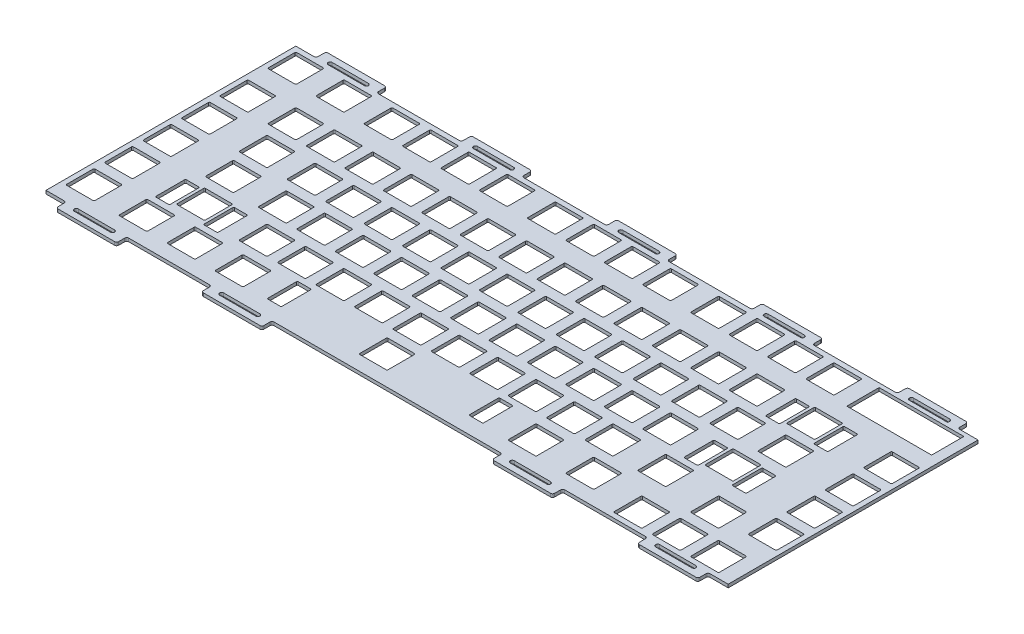
SolidWorks part; units mm, degrees
ref_plane "Front" through (0, 0, 0) normal (0, 0, 1) x (1, 0, 0)
ref_plane "Top" through (0, 0, 0) normal (0, 1, 0) x (1, 0, 0)
ref_plane "Right" through (0, 0, 0) normal (1, 0, 0) x (0, 0, -1)
sketch "Sketch4" plane through (0, 0, 0) normal (0, 1, 0) x (1, 0, 0)
  line L5 (291.1375, -2) -> (333.1375, -2)
  line L6 (291.1375, -2) -> (291.1375, -18)
  line L7 (291.1375, -18) -> (333.1375, -18)
  line L12 (333.1375, -2) -> (333.1375, -18)
  line L202 (0, 0) -> (338.1375, 0)
  line L781 (311.3, -102.25) -> (298.3, -102.25)
  line L782 (335.1125, -97.4875) -> (322.1125, -97.4875)
  line L783 (316.85, -120.8) -> (316.85, -107.8)
  line L784 (330.35, -121.3) -> (317.35, -121.3)
  line L785 (330.85, -107.8) -> (330.85, -120.8)
  line L786 (317.35, -107.3) -> (330.35, -107.3)
  line L787 (297.8, -120.8) -> (297.8, -107.8)
  line L788 (311.3, -121.3) -> (298.3, -121.3)
  line L789 (311.8, -107.8) -> (311.8, -120.8)
  line L790 (298.3, -107.3) -> (311.3, -107.3)
  line L791 (263.675, -116.5375) -> (250.675, -116.5375)
  line L792 (278.75, -120.8) -> (278.75, -107.8)
  line L793 (292.25, -121.3) -> (279.25, -121.3)
  line L794 (292.75, -107.8) -> (292.75, -120.8)
  line L795 (279.25, -107.3) -> (292.25, -107.3)
  line L796 (235.1, -116.5375) -> (222.1, -116.5375)
  line L797 (83.9875, -26.3375) -> (96.9875, -26.3375)
  line L798 (97.4875, -26.8375) -> (97.4875, -39.8375)
  line L799 (96.9875, -40.3375) -> (83.9875, -40.3375)
  line L800 (83.4875, -39.8375) -> (83.4875, -26.8375)
  line L801 (102.5375, -39.8375) -> (102.5375, -26.8375)
  line L802 (116.0375, -40.3375) -> (103.0375, -40.3375)
  line L803 (116.5375, -26.8375) -> (116.5375, -39.8375)
  line L804 (103.0375, -26.3375) -> (116.0375, -26.3375)
  line L805 (188.2625, -58.8875) -> (188.2625, -45.8875)
  line L806 (201.7625, -59.3875) -> (188.7625, -59.3875)
  line L807 (202.2625, -45.8875) -> (202.2625, -58.8875)
  line L808 (188.7625, -45.3875) -> (201.7625, -45.3875)
  line L809 (207.3125, -58.8875) -> (207.3125, -45.8875)
  line L810 (220.8125, -59.3875) -> (207.8125, -59.3875)
  line L811 (221.3125, -45.8875) -> (221.3125, -58.8875)
  line L812 (207.8125, -45.3875) -> (220.8125, -45.3875)
  line L813 (321.6125, -77.9375) -> (321.6125, -64.9375)
  line L814 (335.1125, -78.4375) -> (322.1125, -78.4375)
  line L815 (335.6125, -64.9375) -> (335.6125, -77.9375)
  line L816 (322.1125, -64.4375) -> (335.1125, -64.4375)
  line L817 (148.2812, -102.5375) -> (161.2812, -102.5375)
  line L818 (161.7812, -103.0375) -> (161.7812, -116.0375)
  line L819 (161.2812, -116.5375) -> (148.2812, -116.5375)
  line L820 (147.7812, -116.0375) -> (147.7812, -103.0375)
  line L821 (208.2812, -101.0375) -> (208.2812, -115.0375)
  line L822 (201.7812, -100.5375) -> (207.7812, -100.5375)
  line L823 (201.2812, -115.0375) -> (201.2812, -101.0375)
  line L824 (207.7812, -115.5375) -> (201.7812, -115.5375)
  line L825 (64.4375, -39.8375) -> (64.4375, -26.8375)
  line L826 (77.9375, -40.3375) -> (64.9375, -40.3375)
  line L827 (78.4375, -26.8375) -> (78.4375, -39.8375)
  line L828 (64.9375, -26.3375) -> (77.9375, -26.3375)
  line L829 (169.2125, -58.8875) -> (169.2125, -45.8875)
  line L830 (182.7125, -59.3875) -> (169.7125, -59.3875)
  line L831 (183.2125, -45.8875) -> (183.2125, -58.8875)
  line L832 (169.7125, -45.3875) -> (182.7125, -45.3875)
  line L833 (273.1932, -65.4375) -> (279.1932, -65.4375)
  line L834 (279.6932, -65.9375) -> (279.6932, -79.9375)
  line L835 (279.1932, -80.4375) -> (273.1932, -80.4375)
  line L836 (272.6932, -79.9375) -> (272.6932, -65.9375)
  line L837 (296.5692, -79.9375) -> (296.5692, -65.9375)
  line L838 (303.0692, -80.4375) -> (297.0692, -80.4375)
  line L839 (303.5692, -65.9375) -> (303.5692, -79.9375)
  line L840 (297.0692, -65.4375) -> (303.0692, -65.4375)
  line L841 (76.3437, -116.0375) -> (76.3437, -103.0375)
  line L842 (89.8437, -116.5375) -> (76.8437, -116.5375)
  line L843 (90.3437, -103.0375) -> (90.3437, -116.0375)
  line L844 (76.8437, -102.5375) -> (89.8437, -102.5375)
  line L845 (45.3875, -39.8375) -> (45.3875, -26.8375)
  line L846 (58.8875, -40.3375) -> (45.8875, -40.3375)
  line L847 (59.3875, -26.8375) -> (59.3875, -39.8375)
  line L848 (45.8875, -26.3375) -> (58.8875, -26.3375)
  line L849 (131.6125, -45.3875) -> (144.6125, -45.3875)
  line L850 (145.1125, -45.8875) -> (145.1125, -58.8875)
  line L851 (144.6125, -59.3875) -> (131.6125, -59.3875)
  line L852 (131.1125, -58.8875) -> (131.1125, -45.8875)
  line L853 (150.1625, -58.8875) -> (150.1625, -45.8875)
  line L854 (163.6625, -59.3875) -> (150.6625, -59.3875)
  line L855 (164.1625, -45.8875) -> (164.1625, -58.8875)
  line L856 (150.6625, -45.3875) -> (163.6625, -45.3875)
  line L857 (281.1312, -77.9375) -> (281.1312, -64.9375)
  line L858 (294.6312, -78.4375) -> (281.6312, -78.4375)
  line L859 (295.1312, -64.9375) -> (295.1312, -77.9375)
  line L860 (281.6312, -64.4375) -> (294.6312, -64.4375)
  line L861 (52.5312, -116.0375) -> (52.5312, -103.0375)
  line L862 (66.0312, -116.5375) -> (53.0312, -116.5375)
  line L863 (66.5312, -103.0375) -> (66.5312, -116.0375)
  line L864 (53.0312, -102.5375) -> (66.0312, -102.5375)
  line L865 (3.025, -26.3375) -> (16.025, -26.3375)
  line L866 (16.525, -26.8375) -> (16.525, -39.8375)
  line L867 (16.025, -40.3375) -> (3.025, -40.3375)
  line L868 (2.525, -39.8375) -> (2.525, -26.8375)
  line L869 (26.3375, -39.8375) -> (26.3375, -26.8375)
  line L870 (39.8375, -40.3375) -> (26.8375, -40.3375)
  line L871 (40.3375, -26.8375) -> (40.3375, -39.8375)
  line L872 (26.8375, -26.3375) -> (39.8375, -26.3375)
  line L873 (112.0625, -58.8875) -> (112.0625, -45.8875)
  line L874 (125.5625, -59.3875) -> (112.5625, -59.3875)
  line L875 (126.0625, -45.8875) -> (126.0625, -58.8875)
  line L876 (112.5625, -45.3875) -> (125.5625, -45.3875)
  line L877 (250.175, -77.9375) -> (250.175, -64.9375)
  line L878 (263.675, -78.4375) -> (250.675, -78.4375)
  line L879 (264.175, -64.9375) -> (264.175, -77.9375)
  line L880 (250.675, -64.4375) -> (263.675, -64.4375)
  line L881 (3.025, -102.5375) -> (16.025, -102.5375)
  line L882 (16.525, -103.0375) -> (16.525, -116.0375)
  line L883 (16.025, -116.5375) -> (3.025, -116.5375)
  line L884 (2.525, -116.0375) -> (2.525, -103.0375)
  line L885 (28.7187, -116.0375) -> (28.7187, -103.0375)
  line L886 (42.2187, -116.5375) -> (29.2187, -116.5375)
  line L887 (42.7187, -103.0375) -> (42.7187, -116.0375)
  line L888 (29.2187, -102.5375) -> (42.2187, -102.5375)
  line L893 (93.0125, -58.8875) -> (93.0125, -45.8875)
  line L894 (106.5125, -59.3875) -> (93.5125, -59.3875)
  line L895 (107.0125, -45.8875) -> (107.0125, -58.8875)
  line L896 (93.5125, -45.3875) -> (106.5125, -45.3875)
  line L897 (212.575, -64.4375) -> (225.575, -64.4375)
  line L898 (226.075, -64.9375) -> (226.075, -77.9375)
  line L899 (225.575, -78.4375) -> (212.575, -78.4375)
  line L900 (212.075, -77.9375) -> (212.075, -64.9375)
  line L901 (231.125, -77.9375) -> (231.125, -64.9375)
  line L902 (244.625, -78.4375) -> (231.625, -78.4375)
  line L903 (245.125, -64.9375) -> (245.125, -77.9375)
  line L904 (231.625, -64.4375) -> (244.625, -64.4375)
  line L905 (297.8, -101.75) -> (297.8, -88.75)
  line L906 (311.8, -88.75) -> (311.8, -101.75)
  line L907 (298.3, -88.25) -> (311.3, -88.25)
  line L912 (55.4125, -45.3875) -> (68.4125, -45.3875)
  line L913 (68.9125, -45.8875) -> (68.9125, -58.8875)
  line L914 (68.4125, -59.3875) -> (55.4125, -59.3875)
  line L915 (54.9125, -58.8875) -> (54.9125, -45.8875)
  line L916 (73.9625, -58.8875) -> (73.9625, -45.8875)
  line L917 (87.4625, -59.3875) -> (74.4625, -59.3875)
  line L918 (87.9625, -45.8875) -> (87.9625, -58.8875)
  line L919 (74.4625, -45.3875) -> (87.4625, -45.3875)
  line L920 (193.025, -77.9375) -> (193.025, -64.9375)
  line L921 (206.525, -78.4375) -> (193.525, -78.4375)
  line L922 (207.025, -64.9375) -> (207.025, -77.9375)
  line L923 (193.525, -64.4375) -> (206.525, -64.4375)
  line L924 (321.6125, -96.9875) -> (321.6125, -83.9875)
  line L925 (335.6125, -83.9875) -> (335.6125, -96.9875)
  line L926 (322.1125, -83.4875) -> (335.1125, -83.4875)
  line L927 (269.725, -2.525) -> (282.725, -2.525)
  line L928 (283.225, -3.025) -> (283.225, -16.025)
  line L929 (282.725, -16.525) -> (269.725, -16.525)
  line L930 (269.225, -16.025) -> (269.225, -3.025)
  line L935 (31.1, -58.8875) -> (31.1, -45.8875)
  line L936 (44.6, -59.3875) -> (31.6, -59.3875)
  line L937 (45.1, -45.8875) -> (45.1, -58.8875)
  line L938 (31.6, -45.3875) -> (44.6, -45.3875)
  line L939 (173.975, -77.9375) -> (173.975, -64.9375)
  line L940 (187.475, -78.4375) -> (174.475, -78.4375)
  line L941 (187.975, -64.9375) -> (187.975, -77.9375)
  line L942 (174.475, -64.4375) -> (187.475, -64.4375)
  line L943 (241.15, -83.4875) -> (254.15, -83.4875)
  line L944 (254.65, -83.9875) -> (254.65, -96.9875)
  line L945 (254.15, -97.4875) -> (241.15, -97.4875)
  line L946 (240.65, -96.9875) -> (240.65, -83.9875)
  line L947 (266.8437, -96.9875) -> (266.8437, -83.9875)
  line L948 (280.3437, -97.4875) -> (267.3437, -97.4875)
  line L949 (280.8437, -83.9875) -> (280.8437, -96.9875)
  line L950 (267.3437, -83.4875) -> (280.3437, -83.4875)
  line L951 (250.175, -16.025) -> (250.175, -3.025)
  line L952 (263.675, -16.525) -> (250.675, -16.525)
  line L953 (264.175, -3.025) -> (264.175, -16.025)
  line L954 (250.675, -2.525) -> (263.675, -2.525)
  line L955 (2.525, -58.8875) -> (2.525, -45.8875)
  line L956 (16.025, -59.3875) -> (3.025, -59.3875)
  line L957 (16.525, -45.8875) -> (16.525, -58.8875)
  line L958 (3.025, -45.3875) -> (16.025, -45.3875)
  line L959 (136.375, -64.4375) -> (149.375, -64.4375)
  line L960 (149.875, -64.9375) -> (149.875, -77.9375)
  line L961 (149.375, -78.4375) -> (136.375, -78.4375)
  line L962 (135.875, -77.9375) -> (135.875, -64.9375)
  line L963 (154.925, -77.9375) -> (154.925, -64.9375)
  line L964 (168.425, -78.4375) -> (155.425, -78.4375)
  line L965 (168.925, -64.9375) -> (168.925, -77.9375)
  line L966 (155.425, -64.4375) -> (168.425, -64.4375)
  line L967 (221.6, -96.9875) -> (221.6, -83.9875)
  line L968 (235.1, -97.4875) -> (222.1, -97.4875)
  line L969 (235.6, -83.9875) -> (235.6, -96.9875)
  line L970 (222.1, -83.4875) -> (235.1, -83.4875)
  line L971 (231.125, -16.025) -> (231.125, -3.025)
  line L972 (244.625, -16.525) -> (231.625, -16.525)
  line L973 (245.125, -3.025) -> (245.125, -16.025)
  line L974 (231.625, -2.525) -> (244.625, -2.525)
  line L975 (299.4505, -27.3375) -> (305.4505, -27.3375)
  line L976 (305.9505, -27.8375) -> (305.9505, -41.8375)
  line L977 (305.4505, -42.3375) -> (299.4505, -42.3375)
  line L978 (298.9505, -41.8375) -> (298.9505, -27.8375)
  line L979 (321.6125, -39.8375) -> (321.6125, -26.8375)
  line L980 (335.1125, -40.3375) -> (322.1125, -40.3375)
  line L981 (335.6125, -26.8375) -> (335.6125, -39.8375)
  line L982 (322.1125, -26.3375) -> (335.1125, -26.3375)
  line L983 (116.825, -77.9375) -> (116.825, -64.9375)
  line L984 (130.325, -78.4375) -> (117.325, -78.4375)
  line L985 (130.825, -64.9375) -> (130.825, -77.9375)
  line L986 (117.325, -64.4375) -> (130.325, -64.4375)
  line L987 (202.55, -96.9875) -> (202.55, -83.9875)
  line L988 (216.05, -97.4875) -> (203.05, -97.4875)
  line L989 (216.55, -83.9875) -> (216.55, -96.9875)
  line L990 (203.05, -83.4875) -> (216.05, -83.4875)
  line L991 (188.7625, -2.525) -> (201.7625, -2.525)
  line L992 (202.2625, -3.025) -> (202.2625, -16.025)
  line L993 (201.7625, -16.525) -> (188.7625, -16.525)
  line L994 (188.2625, -16.025) -> (188.2625, -3.025)
  line L995 (212.075, -16.025) -> (212.075, -3.025)
  line L996 (225.575, -16.525) -> (212.575, -16.525)
  line L997 (226.075, -3.025) -> (226.075, -16.025)
  line L998 (212.575, -2.525) -> (225.575, -2.525)
  line L999 (275.0745, -41.8375) -> (275.0745, -27.8375)
  line L1000 (281.5745, -42.3375) -> (275.5745, -42.3375)
  line L1001 (282.0745, -27.8375) -> (282.0745, -41.8375)
  line L1002 (275.5745, -27.3375) -> (281.5745, -27.3375)
  line L1003 (97.775, -77.9375) -> (97.775, -64.9375)
  line L1004 (111.275, -78.4375) -> (98.275, -78.4375)
  line L1005 (111.775, -64.9375) -> (111.775, -77.9375)
  line L1006 (98.275, -64.4375) -> (111.275, -64.4375)
  line L1007 (164.95, -83.4875) -> (177.95, -83.4875)
  line L1008 (178.45, -83.9875) -> (178.45, -96.9875)
  line L1009 (177.95, -97.4875) -> (164.95, -97.4875)
  line L1010 (164.45, -96.9875) -> (164.45, -83.9875)
  line L1011 (183.5, -96.9875) -> (183.5, -83.9875)
  line L1012 (197, -97.4875) -> (184, -97.4875)
  line L1013 (197.5, -83.9875) -> (197.5, -96.9875)
  line L1014 (184, -83.4875) -> (197, -83.4875)
  line L1015 (169.2125, -16.025) -> (169.2125, -3.025)
  line L1016 (182.7125, -16.525) -> (169.7125, -16.525)
  line L1017 (183.2125, -3.025) -> (183.2125, -16.025)
  line L1018 (169.7125, -2.525) -> (182.7125, -2.525)
  line L1019 (283.5125, -39.8375) -> (283.5125, -26.8375)
  line L1020 (297.0125, -40.3375) -> (284.0125, -40.3375)
  line L1021 (297.5125, -26.8375) -> (297.5125, -39.8375)
  line L1022 (284.0125, -26.3375) -> (297.0125, -26.3375)
  line L1023 (60.175, -64.4375) -> (73.175, -64.4375)
  line L1024 (73.675, -64.9375) -> (73.675, -77.9375)
  line L1025 (73.175, -78.4375) -> (60.175, -78.4375)
  line L1026 (59.675, -77.9375) -> (59.675, -64.9375)
  line L1027 (78.725, -77.9375) -> (78.725, -64.9375)
  line L1028 (92.225, -78.4375) -> (79.225, -78.4375)
  line L1029 (92.725, -64.9375) -> (92.725, -77.9375)
  line L1030 (79.225, -64.4375) -> (92.225, -64.4375)
  line L1031 (145.4, -96.9875) -> (145.4, -83.9875)
  line L1032 (158.9, -97.4875) -> (145.9, -97.4875)
  line L1033 (159.4, -83.9875) -> (159.4, -96.9875)
  line L1034 (145.9, -83.4875) -> (158.9, -83.4875)
  line L1035 (150.1625, -16.025) -> (150.1625, -3.025)
  line L1036 (163.6625, -16.525) -> (150.6625, -16.525)
  line L1037 (164.1625, -3.025) -> (164.1625, -16.025)
  line L1038 (150.6625, -2.525) -> (163.6625, -2.525)
  line L1039 (236.3875, -26.3375) -> (249.3875, -26.3375)
  line L1040 (249.8875, -26.8375) -> (249.8875, -39.8375)
  line L1041 (249.3875, -40.3375) -> (236.3875, -40.3375)
  line L1042 (235.8875, -39.8375) -> (235.8875, -26.8375)
  line L1043 (254.9375, -39.8375) -> (254.9375, -26.8375)
  line L1044 (268.4375, -40.3375) -> (255.4375, -40.3375)
  line L1045 (268.9375, -26.8375) -> (268.9375, -39.8375)
  line L1046 (255.4375, -26.3375) -> (268.4375, -26.3375)
  line L1047 (33.4812, -77.9375) -> (33.4812, -64.9375)
  line L1048 (46.9812, -78.4375) -> (33.9812, -78.4375)
  line L1049 (47.4812, -64.9375) -> (47.4812, -77.9375)
  line L1050 (33.9812, -64.4375) -> (46.9812, -64.4375)
  line L1051 (126.35, -96.9875) -> (126.35, -83.9875)
  line L1052 (139.85, -97.4875) -> (126.85, -97.4875)
  line L1053 (140.35, -83.9875) -> (140.35, -96.9875)
  line L1054 (126.85, -83.4875) -> (139.85, -83.4875)
  line L1055 (107.8, -2.525) -> (120.8, -2.525)
  line L1056 (121.3, -3.025) -> (121.3, -16.025)
  line L1057 (120.8, -16.525) -> (107.8, -16.525)
  line L1058 (107.3, -16.025) -> (107.3, -3.025)
  line L1059 (131.1125, -16.025) -> (131.1125, -3.025)
  line L1060 (144.6125, -16.525) -> (131.6125, -16.525)
  line L1061 (145.1125, -3.025) -> (145.1125, -16.025)
  line L1062 (131.6125, -2.525) -> (144.6125, -2.525)
  line L1063 (216.8375, -39.8375) -> (216.8375, -26.8375)
  line L1064 (230.3375, -40.3375) -> (217.3375, -40.3375)
  line L1065 (230.8375, -26.8375) -> (230.8375, -39.8375)
  line L1066 (217.3375, -26.3375) -> (230.3375, -26.3375)
  line L1067 (2.525, -77.9375) -> (2.525, -64.9375)
  line L1068 (16.025, -78.4375) -> (3.025, -78.4375)
  line L1069 (16.525, -64.9375) -> (16.525, -77.9375)
  line L1070 (3.025, -64.4375) -> (16.025, -64.4375)
  line L1071 (88.75, -83.4875) -> (101.75, -83.4875)
  line L1072 (102.25, -83.9875) -> (102.25, -96.9875)
  line L1073 (101.75, -97.4875) -> (88.75, -97.4875)
  line L1074 (88.25, -96.9875) -> (88.25, -83.9875)
  line L1075 (107.3, -96.9875) -> (107.3, -83.9875)
  line L1076 (120.8, -97.4875) -> (107.8, -97.4875)
  line L1077 (121.3, -83.9875) -> (121.3, -96.9875)
  line L1078 (107.8, -83.4875) -> (120.8, -83.4875)
  line L1079 (0, -123.825) -> (0, 0)
  line L1080 (338.1375, 0) -> (338.1375, -123.825)
  line L1081 (338.1375, -123.825) -> (0, -123.825)
  line L1082 (88.25, -16.025) -> (88.25, -3.025)
  line L1083 (101.75, -16.525) -> (88.75, -16.525)
  line L1084 (102.25, -3.025) -> (102.25, -16.025)
  line L1085 (88.75, -2.525) -> (101.75, -2.525)
  line L1086 (197.7875, -39.8375) -> (197.7875, -26.8375)
  line L1087 (211.2875, -40.3375) -> (198.2875, -40.3375)
  line L1088 (211.7875, -26.8375) -> (211.7875, -39.8375)
  line L1089 (198.2875, -26.3375) -> (211.2875, -26.3375)
  line L1090 (288.775, -45.3875) -> (301.775, -45.3875)
  line L1091 (302.275, -45.8875) -> (302.275, -58.8875)
  line L1092 (301.775, -59.3875) -> (288.775, -59.3875)
  line L1093 (288.275, -58.8875) -> (288.275, -45.8875)
  line L1094 (321.6125, -58.8875) -> (321.6125, -45.8875)
  line L1095 (335.1125, -59.3875) -> (322.1125, -59.3875)
  line L1096 (335.6125, -45.8875) -> (335.6125, -58.8875)
  line L1097 (322.1125, -45.3875) -> (335.1125, -45.3875)
  line L1098 (69.2, -96.9875) -> (69.2, -83.9875)
  line L1099 (82.7, -97.4875) -> (69.7, -97.4875)
  line L1100 (83.2, -83.9875) -> (83.2, -96.9875)
  line L1101 (69.7, -83.4875) -> (82.7, -83.4875)
  line L1102 (69.2, -16.025) -> (69.2, -3.025)
  line L1103 (82.7, -16.525) -> (69.7, -16.525)
  line L1104 (83.2, -3.025) -> (83.2, -16.025)
  line L1105 (69.7, -2.525) -> (82.7, -2.525)
  line L1106 (160.1875, -26.3375) -> (173.1875, -26.3375)
  line L1107 (173.6875, -26.8375) -> (173.6875, -39.8375)
  line L1108 (173.1875, -40.3375) -> (160.1875, -40.3375)
  line L1109 (159.6875, -39.8375) -> (159.6875, -26.8375)
  line L1110 (178.7375, -39.8375) -> (178.7375, -26.8375)
  line L1111 (192.2375, -40.3375) -> (179.2375, -40.3375)
  line L1112 (192.7375, -26.8375) -> (192.7375, -39.8375)
  line L1113 (179.2375, -26.3375) -> (192.2375, -26.3375)
  line L1114 (264.4625, -58.8875) -> (264.4625, -45.8875)
  line L1115 (277.9625, -59.3875) -> (264.9625, -59.3875)
  line L1116 (278.4625, -45.8875) -> (278.4625, -58.8875)
  line L1117 (264.9625, -45.3875) -> (277.9625, -45.3875)
  line L1118 (53.6817, -98.9875) -> (53.6817, -84.9875)
  line L1119 (60.1817, -99.4875) -> (54.1817, -99.4875)
  line L1120 (60.6817, -84.9875) -> (60.6817, -98.9875)
  line L1121 (54.1817, -84.4875) -> (60.1817, -84.4875)
  line L1122 (250.675, -102.5375) -> (263.675, -102.5375)
  line L1123 (264.175, -103.0375) -> (264.175, -116.0375)
  line L1124 (250.175, -116.0375) -> (250.175, -103.0375)
  line L1125 (26.8375, -2.525) -> (39.8375, -2.525)
  line L1126 (40.3375, -3.025) -> (40.3375, -16.025)
  line L1127 (39.8375, -16.525) -> (26.8375, -16.525)
  line L1128 (26.3375, -16.025) -> (26.3375, -3.025)
  line L1129 (50.15, -16.025) -> (50.15, -3.025)
  line L1130 (63.65, -16.525) -> (50.65, -16.525)
  line L1131 (64.15, -3.025) -> (64.15, -16.025)
  line L1132 (50.65, -2.525) -> (63.65, -2.525)
  line L1133 (140.6375, -39.8375) -> (140.6375, -26.8375)
  line L1134 (154.1375, -40.3375) -> (141.1375, -40.3375)
  line L1135 (154.6375, -26.8375) -> (154.6375, -39.8375)
  line L1136 (141.1375, -26.3375) -> (154.1375, -26.3375)
  line L1137 (245.4125, -58.8875) -> (245.4125, -45.8875)
  line L1138 (258.9125, -59.3875) -> (245.9125, -59.3875)
  line L1139 (259.4125, -45.8875) -> (259.4125, -58.8875)
  line L1140 (245.9125, -45.3875) -> (258.9125, -45.3875)
  line L1141 (38.7437, -83.4875) -> (51.7437, -83.4875)
  line L1142 (52.2437, -83.9875) -> (52.2437, -96.9875)
  line L1143 (51.7437, -97.4875) -> (38.7437, -97.4875)
  line L1144 (38.2437, -96.9875) -> (38.2437, -83.9875)
  line L1145 (29.8057, -98.9875) -> (29.8057, -84.9875)
  line L1146 (36.3057, -99.4875) -> (30.3057, -99.4875)
  line L1147 (36.8057, -84.9875) -> (36.8057, -98.9875)
  line L1148 (30.3057, -84.4875) -> (36.3057, -84.4875)
  line L1149 (221.6, -116.0375) -> (221.6, -103.0375)
  line L1150 (235.6, -103.0375) -> (235.6, -116.0375)
  line L1151 (222.1, -102.5375) -> (235.1, -102.5375)
  line L1152 (121.5875, -39.8375) -> (121.5875, -26.8375)
  line L1153 (135.0875, -40.3375) -> (122.0875, -40.3375)
  line L1154 (135.5875, -26.8375) -> (135.5875, -39.8375)
  line L1155 (122.0875, -26.3375) -> (135.0875, -26.3375)
  line L1156 (226.3625, -58.8875) -> (226.3625, -45.8875)
  line L1157 (239.8625, -59.3875) -> (226.8625, -59.3875)
  line L1158 (240.3625, -45.8875) -> (240.3625, -58.8875)
  line L1159 (226.8625, -45.3875) -> (239.8625, -45.3875)
  line L1160 (2.525, -96.9875) -> (2.525, -83.9875)
  line L1161 (16.025, -97.4875) -> (3.025, -97.4875)
  line L1162 (16.525, -83.9875) -> (16.525, -96.9875)
  line L1163 (3.025, -83.4875) -> (16.025, -83.4875)
  line L1164 (108.2812, -101.0375) -> (108.2812, -115.0375)
  line L1165 (101.7812, -100.5375) -> (107.7812, -100.5375)
  line L1166 (101.2812, -115.0375) -> (101.2812, -101.0375)
  line L1167 (107.7812, -115.5375) -> (101.7812, -115.5375)
  line L1168 (16.525, -16.025) -> (16.525, -3.025)
  line L1169 (3.025, -16.525) -> (16.025, -16.525)
  line L1170 (2.525, -3.025) -> (2.525, -16.025)
  line L1171 (16.025, -2.525) -> (3.025, -2.525)
  arc A776 (298.3, -102.25) -> (297.8, -101.75) centre (298.3, -101.75) cw
  arc A777 (311.8, -101.75) -> (311.3, -102.25) centre (311.3, -101.75) cw
  arc A778 (322.1125, -97.4875) -> (321.6125, -96.9875) centre (322.1125, -96.9875) cw
  arc A779 (335.6125, -96.9875) -> (335.1125, -97.4875) centre (335.1125, -96.9875) cw
  arc A780 (316.85, -107.8) -> (317.35, -107.3) centre (317.35, -107.8) cw
  arc A781 (317.35, -121.3) -> (316.85, -120.8) centre (317.35, -120.8) cw
  arc A782 (330.85, -120.8) -> (330.35, -121.3) centre (330.35, -120.8) cw
  arc A783 (330.35, -107.3) -> (330.85, -107.8) centre (330.35, -107.8) cw
  arc A784 (297.8, -107.8) -> (298.3, -107.3) centre (298.3, -107.8) cw
  arc A785 (298.3, -121.3) -> (297.8, -120.8) centre (298.3, -120.8) cw
  arc A786 (311.8, -120.8) -> (311.3, -121.3) centre (311.3, -120.8) cw
  arc A787 (311.3, -107.3) -> (311.8, -107.8) centre (311.3, -107.8) cw
  arc A788 (264.175, -116.0375) -> (263.675, -116.5375) centre (263.675, -116.0375) cw
  arc A789 (250.675, -116.5375) -> (250.175, -116.0375) centre (250.675, -116.0375) cw
  arc A790 (278.75, -107.8) -> (279.25, -107.3) centre (279.25, -107.8) cw
  arc A791 (279.25, -121.3) -> (278.75, -120.8) centre (279.25, -120.8) cw
  arc A792 (292.75, -120.8) -> (292.25, -121.3) centre (292.25, -120.8) cw
  arc A793 (292.25, -107.3) -> (292.75, -107.8) centre (292.25, -107.8) cw
  arc A794 (222.1, -116.5375) -> (221.6, -116.0375) centre (222.1, -116.0375) cw
  arc A795 (235.6, -116.0375) -> (235.1, -116.5375) centre (235.1, -116.0375) cw
  arc A796 (2.525, -3.025) -> (3.025, -2.525) centre (3.025, -3.025) cw
  arc A797 (16.025, -2.525) -> (16.525, -3.025) centre (16.025, -3.025) cw
  arc A798 (3.025, -16.525) -> (2.525, -16.025) centre (3.025, -16.025) cw
  arc A799 (16.525, -16.025) -> (16.025, -16.525) centre (16.025, -16.025) cw
  arc A800 (83.4875, -26.8375) -> (83.9875, -26.3375) centre (83.9875, -26.8375) cw
  arc A801 (96.9875, -26.3375) -> (97.4875, -26.8375) centre (96.9875, -26.8375) cw
  arc A802 (97.4875, -39.8375) -> (96.9875, -40.3375) centre (96.9875, -39.8375) cw
  arc A803 (83.9875, -40.3375) -> (83.4875, -39.8375) centre (83.9875, -39.8375) cw
  arc A804 (102.5375, -26.8375) -> (103.0375, -26.3375) centre (103.0375, -26.8375) cw
  arc A805 (103.0375, -40.3375) -> (102.5375, -39.8375) centre (103.0375, -39.8375) cw
  arc A806 (116.5375, -39.8375) -> (116.0375, -40.3375) centre (116.0375, -39.8375) cw
  arc A807 (116.0375, -26.3375) -> (116.5375, -26.8375) centre (116.0375, -26.8375) cw
  arc A808 (188.2625, -45.8875) -> (188.7625, -45.3875) centre (188.7625, -45.8875) cw
  arc A809 (188.7625, -59.3875) -> (188.2625, -58.8875) centre (188.7625, -58.8875) cw
  arc A810 (202.2625, -58.8875) -> (201.7625, -59.3875) centre (201.7625, -58.8875) cw
  arc A811 (201.7625, -45.3875) -> (202.2625, -45.8875) centre (201.7625, -45.8875) cw
  arc A812 (207.3125, -45.8875) -> (207.8125, -45.3875) centre (207.8125, -45.8875) cw
  arc A813 (207.8125, -59.3875) -> (207.3125, -58.8875) centre (207.8125, -58.8875) cw
  arc A814 (221.3125, -58.8875) -> (220.8125, -59.3875) centre (220.8125, -58.8875) cw
  arc A815 (220.8125, -45.3875) -> (221.3125, -45.8875) centre (220.8125, -45.8875) cw
  arc A816 (321.6125, -64.9375) -> (322.1125, -64.4375) centre (322.1125, -64.9375) cw
  arc A817 (322.1125, -78.4375) -> (321.6125, -77.9375) centre (322.1125, -77.9375) cw
  arc A818 (335.6125, -77.9375) -> (335.1125, -78.4375) centre (335.1125, -77.9375) cw
  arc A819 (335.1125, -64.4375) -> (335.6125, -64.9375) centre (335.1125, -64.9375) cw
  arc A820 (147.7812, -103.0375) -> (148.2812, -102.5375) centre (148.2812, -103.0375) cw
  arc A821 (161.2812, -102.5375) -> (161.7812, -103.0375) centre (161.2812, -103.0375) cw
  arc A822 (161.7812, -116.0375) -> (161.2812, -116.5375) centre (161.2812, -116.0375) cw
  arc A823 (148.2812, -116.5375) -> (147.7812, -116.0375) centre (148.2812, -116.0375) cw
  arc A824 (208.2812, -115.0375) -> (207.7812, -115.5375) centre (207.7812, -115.0375) cw
  arc A825 (207.7812, -100.5375) -> (208.2812, -101.0375) centre (207.7812, -101.0375) cw
  arc A826 (201.2812, -101.0375) -> (201.7812, -100.5375) centre (201.7812, -101.0375) cw
  arc A827 (201.7812, -115.5375) -> (201.2812, -115.0375) centre (201.7812, -115.0375) cw
  arc A828 (64.4375, -26.8375) -> (64.9375, -26.3375) centre (64.9375, -26.8375) cw
  arc A829 (64.9375, -40.3375) -> (64.4375, -39.8375) centre (64.9375, -39.8375) cw
  arc A830 (78.4375, -39.8375) -> (77.9375, -40.3375) centre (77.9375, -39.8375) cw
  arc A831 (77.9375, -26.3375) -> (78.4375, -26.8375) centre (77.9375, -26.8375) cw
  arc A832 (169.2125, -45.8875) -> (169.7125, -45.3875) centre (169.7125, -45.8875) cw
  arc A833 (169.7125, -59.3875) -> (169.2125, -58.8875) centre (169.7125, -58.8875) cw
  arc A834 (183.2125, -58.8875) -> (182.7125, -59.3875) centre (182.7125, -58.8875) cw
  arc A835 (182.7125, -45.3875) -> (183.2125, -45.8875) centre (182.7125, -45.8875) cw
  arc A836 (272.6932, -65.9375) -> (273.1932, -65.4375) centre (273.1932, -65.9375) cw
  arc A837 (279.1932, -65.4375) -> (279.6932, -65.9375) centre (279.1932, -65.9375) cw
  arc A838 (279.6932, -79.9375) -> (279.1932, -80.4375) centre (279.1932, -79.9375) cw
  arc A839 (273.1932, -80.4375) -> (272.6932, -79.9375) centre (273.1932, -79.9375) cw
  arc A840 (296.5692, -65.9375) -> (297.0692, -65.4375) centre (297.0692, -65.9375) cw
  arc A841 (297.0692, -80.4375) -> (296.5692, -79.9375) centre (297.0692, -79.9375) cw
  arc A842 (303.5692, -79.9375) -> (303.0692, -80.4375) centre (303.0692, -79.9375) cw
  arc A843 (303.0692, -65.4375) -> (303.5692, -65.9375) centre (303.0692, -65.9375) cw
  arc A844 (76.3437, -103.0375) -> (76.8437, -102.5375) centre (76.8437, -103.0375) cw
  arc A845 (76.8437, -116.5375) -> (76.3437, -116.0375) centre (76.8437, -116.0375) cw
  arc A846 (90.3437, -116.0375) -> (89.8437, -116.5375) centre (89.8437, -116.0375) cw
  arc A847 (89.8437, -102.5375) -> (90.3437, -103.0375) centre (89.8437, -103.0375) cw
  arc A848 (45.3875, -26.8375) -> (45.8875, -26.3375) centre (45.8875, -26.8375) cw
  arc A849 (45.8875, -40.3375) -> (45.3875, -39.8375) centre (45.8875, -39.8375) cw
  arc A850 (59.3875, -39.8375) -> (58.8875, -40.3375) centre (58.8875, -39.8375) cw
  arc A851 (58.8875, -26.3375) -> (59.3875, -26.8375) centre (58.8875, -26.8375) cw
  arc A852 (131.1125, -45.8875) -> (131.6125, -45.3875) centre (131.6125, -45.8875) cw
  arc A853 (144.6125, -45.3875) -> (145.1125, -45.8875) centre (144.6125, -45.8875) cw
  arc A854 (145.1125, -58.8875) -> (144.6125, -59.3875) centre (144.6125, -58.8875) cw
  arc A855 (131.6125, -59.3875) -> (131.1125, -58.8875) centre (131.6125, -58.8875) cw
  arc A856 (150.1625, -45.8875) -> (150.6625, -45.3875) centre (150.6625, -45.8875) cw
  arc A857 (150.6625, -59.3875) -> (150.1625, -58.8875) centre (150.6625, -58.8875) cw
  arc A858 (164.1625, -58.8875) -> (163.6625, -59.3875) centre (163.6625, -58.8875) cw
  arc A859 (163.6625, -45.3875) -> (164.1625, -45.8875) centre (163.6625, -45.8875) cw
  arc A860 (281.1312, -64.9375) -> (281.6312, -64.4375) centre (281.6312, -64.9375) cw
  arc A861 (281.6312, -78.4375) -> (281.1312, -77.9375) centre (281.6312, -77.9375) cw
  arc A862 (295.1312, -77.9375) -> (294.6312, -78.4375) centre (294.6312, -77.9375) cw
  arc A863 (294.6312, -64.4375) -> (295.1312, -64.9375) centre (294.6312, -64.9375) cw
  arc A864 (52.5312, -103.0375) -> (53.0312, -102.5375) centre (53.0312, -103.0375) cw
  arc A865 (53.0312, -116.5375) -> (52.5312, -116.0375) centre (53.0312, -116.0375) cw
  arc A866 (66.5312, -116.0375) -> (66.0312, -116.5375) centre (66.0312, -116.0375) cw
  arc A867 (66.0312, -102.5375) -> (66.5312, -103.0375) centre (66.0312, -103.0375) cw
  arc A868 (2.525, -26.8375) -> (3.025, -26.3375) centre (3.025, -26.8375) cw
  arc A869 (16.025, -26.3375) -> (16.525, -26.8375) centre (16.025, -26.8375) cw
  arc A870 (16.525, -39.8375) -> (16.025, -40.3375) centre (16.025, -39.8375) cw
  arc A871 (3.025, -40.3375) -> (2.525, -39.8375) centre (3.025, -39.8375) cw
  arc A872 (26.3375, -26.8375) -> (26.8375, -26.3375) centre (26.8375, -26.8375) cw
  arc A873 (26.8375, -40.3375) -> (26.3375, -39.8375) centre (26.8375, -39.8375) cw
  arc A874 (40.3375, -39.8375) -> (39.8375, -40.3375) centre (39.8375, -39.8375) cw
  arc A875 (39.8375, -26.3375) -> (40.3375, -26.8375) centre (39.8375, -26.8375) cw
  arc A876 (112.0625, -45.8875) -> (112.5625, -45.3875) centre (112.5625, -45.8875) cw
  arc A877 (112.5625, -59.3875) -> (112.0625, -58.8875) centre (112.5625, -58.8875) cw
  arc A878 (126.0625, -58.8875) -> (125.5625, -59.3875) centre (125.5625, -58.8875) cw
  arc A879 (125.5625, -45.3875) -> (126.0625, -45.8875) centre (125.5625, -45.8875) cw
  arc A880 (250.175, -64.9375) -> (250.675, -64.4375) centre (250.675, -64.9375) cw
  arc A881 (250.675, -78.4375) -> (250.175, -77.9375) centre (250.675, -77.9375) cw
  arc A882 (264.175, -77.9375) -> (263.675, -78.4375) centre (263.675, -77.9375) cw
  arc A883 (263.675, -64.4375) -> (264.175, -64.9375) centre (263.675, -64.9375) cw
  arc A884 (2.525, -103.0375) -> (3.025, -102.5375) centre (3.025, -103.0375) cw
  arc A885 (16.025, -102.5375) -> (16.525, -103.0375) centre (16.025, -103.0375) cw
  arc A886 (16.525, -116.0375) -> (16.025, -116.5375) centre (16.025, -116.0375) cw
  arc A887 (3.025, -116.5375) -> (2.525, -116.0375) centre (3.025, -116.0375) cw
  arc A888 (28.7187, -103.0375) -> (29.2187, -102.5375) centre (29.2187, -103.0375) cw
  arc A889 (29.2187, -116.5375) -> (28.7187, -116.0375) centre (29.2187, -116.0375) cw
  arc A890 (42.7187, -116.0375) -> (42.2187, -116.5375) centre (42.2187, -116.0375) cw
  arc A891 (42.2187, -102.5375) -> (42.7187, -103.0375) centre (42.2187, -103.0375) cw
  arc A896 (93.0125, -45.8875) -> (93.5125, -45.3875) centre (93.5125, -45.8875) cw
  arc A897 (93.5125, -59.3875) -> (93.0125, -58.8875) centre (93.5125, -58.8875) cw
  arc A898 (107.0125, -58.8875) -> (106.5125, -59.3875) centre (106.5125, -58.8875) cw
  arc A899 (106.5125, -45.3875) -> (107.0125, -45.8875) centre (106.5125, -45.8875) cw
  arc A900 (212.075, -64.9375) -> (212.575, -64.4375) centre (212.575, -64.9375) cw
  arc A901 (225.575, -64.4375) -> (226.075, -64.9375) centre (225.575, -64.9375) cw
  arc A902 (226.075, -77.9375) -> (225.575, -78.4375) centre (225.575, -77.9375) cw
  arc A903 (212.575, -78.4375) -> (212.075, -77.9375) centre (212.575, -77.9375) cw
  arc A904 (231.125, -64.9375) -> (231.625, -64.4375) centre (231.625, -64.9375) cw
  arc A905 (231.625, -78.4375) -> (231.125, -77.9375) centre (231.625, -77.9375) cw
  arc A906 (245.125, -77.9375) -> (244.625, -78.4375) centre (244.625, -77.9375) cw
  arc A907 (244.625, -64.4375) -> (245.125, -64.9375) centre (244.625, -64.9375) cw
  arc A908 (297.8, -88.75) -> (298.3, -88.25) centre (298.3, -88.75) cw
  arc A909 (311.3, -88.25) -> (311.8, -88.75) centre (311.3, -88.75) cw
  arc A914 (54.9125, -45.8875) -> (55.4125, -45.3875) centre (55.4125, -45.8875) cw
  arc A915 (68.4125, -45.3875) -> (68.9125, -45.8875) centre (68.4125, -45.8875) cw
  arc A916 (68.9125, -58.8875) -> (68.4125, -59.3875) centre (68.4125, -58.8875) cw
  arc A917 (55.4125, -59.3875) -> (54.9125, -58.8875) centre (55.4125, -58.8875) cw
  arc A918 (73.9625, -45.8875) -> (74.4625, -45.3875) centre (74.4625, -45.8875) cw
  arc A919 (74.4625, -59.3875) -> (73.9625, -58.8875) centre (74.4625, -58.8875) cw
  arc A920 (87.9625, -58.8875) -> (87.4625, -59.3875) centre (87.4625, -58.8875) cw
  arc A921 (87.4625, -45.3875) -> (87.9625, -45.8875) centre (87.4625, -45.8875) cw
  arc A922 (193.025, -64.9375) -> (193.525, -64.4375) centre (193.525, -64.9375) cw
  arc A923 (193.525, -78.4375) -> (193.025, -77.9375) centre (193.525, -77.9375) cw
  arc A924 (207.025, -77.9375) -> (206.525, -78.4375) centre (206.525, -77.9375) cw
  arc A925 (206.525, -64.4375) -> (207.025, -64.9375) centre (206.525, -64.9375) cw
  arc A926 (321.6125, -83.9875) -> (322.1125, -83.4875) centre (322.1125, -83.9875) cw
  arc A927 (335.1125, -83.4875) -> (335.6125, -83.9875) centre (335.1125, -83.9875) cw
  arc A928 (269.225, -3.025) -> (269.725, -2.525) centre (269.725, -3.025) cw
  arc A929 (282.725, -2.525) -> (283.225, -3.025) centre (282.725, -3.025) cw
  arc A930 (283.225, -16.025) -> (282.725, -16.525) centre (282.725, -16.025) cw
  arc A931 (269.725, -16.525) -> (269.225, -16.025) centre (269.725, -16.025) cw
  arc A936 (31.1, -45.8875) -> (31.6, -45.3875) centre (31.6, -45.8875) cw
  arc A937 (31.6, -59.3875) -> (31.1, -58.8875) centre (31.6, -58.8875) cw
  arc A938 (45.1, -58.8875) -> (44.6, -59.3875) centre (44.6, -58.8875) cw
  arc A939 (44.6, -45.3875) -> (45.1, -45.8875) centre (44.6, -45.8875) cw
  arc A940 (173.975, -64.9375) -> (174.475, -64.4375) centre (174.475, -64.9375) cw
  arc A941 (174.475, -78.4375) -> (173.975, -77.9375) centre (174.475, -77.9375) cw
  arc A942 (187.975, -77.9375) -> (187.475, -78.4375) centre (187.475, -77.9375) cw
  arc A943 (187.475, -64.4375) -> (187.975, -64.9375) centre (187.475, -64.9375) cw
  arc A944 (240.65, -83.9875) -> (241.15, -83.4875) centre (241.15, -83.9875) cw
  arc A945 (254.15, -83.4875) -> (254.65, -83.9875) centre (254.15, -83.9875) cw
  arc A946 (254.65, -96.9875) -> (254.15, -97.4875) centre (254.15, -96.9875) cw
  arc A947 (241.15, -97.4875) -> (240.65, -96.9875) centre (241.15, -96.9875) cw
  arc A948 (266.8437, -83.9875) -> (267.3437, -83.4875) centre (267.3437, -83.9875) cw
  arc A949 (267.3437, -97.4875) -> (266.8437, -96.9875) centre (267.3437, -96.9875) cw
  arc A950 (280.8437, -96.9875) -> (280.3437, -97.4875) centre (280.3437, -96.9875) cw
  arc A951 (280.3437, -83.4875) -> (280.8437, -83.9875) centre (280.3437, -83.9875) cw
  arc A952 (250.175, -3.025) -> (250.675, -2.525) centre (250.675, -3.025) cw
  arc A953 (250.675, -16.525) -> (250.175, -16.025) centre (250.675, -16.025) cw
  arc A954 (264.175, -16.025) -> (263.675, -16.525) centre (263.675, -16.025) cw
  arc A955 (263.675, -2.525) -> (264.175, -3.025) centre (263.675, -3.025) cw
  arc A956 (2.525, -45.8875) -> (3.025, -45.3875) centre (3.025, -45.8875) cw
  arc A957 (3.025, -59.3875) -> (2.525, -58.8875) centre (3.025, -58.8875) cw
  arc A958 (16.525, -58.8875) -> (16.025, -59.3875) centre (16.025, -58.8875) cw
  arc A959 (16.025, -45.3875) -> (16.525, -45.8875) centre (16.025, -45.8875) cw
  arc A960 (135.875, -64.9375) -> (136.375, -64.4375) centre (136.375, -64.9375) cw
  arc A961 (149.375, -64.4375) -> (149.875, -64.9375) centre (149.375, -64.9375) cw
  arc A962 (149.875, -77.9375) -> (149.375, -78.4375) centre (149.375, -77.9375) cw
  arc A963 (136.375, -78.4375) -> (135.875, -77.9375) centre (136.375, -77.9375) cw
  arc A964 (154.925, -64.9375) -> (155.425, -64.4375) centre (155.425, -64.9375) cw
  arc A965 (155.425, -78.4375) -> (154.925, -77.9375) centre (155.425, -77.9375) cw
  arc A966 (168.925, -77.9375) -> (168.425, -78.4375) centre (168.425, -77.9375) cw
  arc A967 (168.425, -64.4375) -> (168.925, -64.9375) centre (168.425, -64.9375) cw
  arc A968 (221.6, -83.9875) -> (222.1, -83.4875) centre (222.1, -83.9875) cw
  arc A969 (222.1, -97.4875) -> (221.6, -96.9875) centre (222.1, -96.9875) cw
  arc A970 (235.6, -96.9875) -> (235.1, -97.4875) centre (235.1, -96.9875) cw
  arc A971 (235.1, -83.4875) -> (235.6, -83.9875) centre (235.1, -83.9875) cw
  arc A972 (231.125, -3.025) -> (231.625, -2.525) centre (231.625, -3.025) cw
  arc A973 (231.625, -16.525) -> (231.125, -16.025) centre (231.625, -16.025) cw
  arc A974 (245.125, -16.025) -> (244.625, -16.525) centre (244.625, -16.025) cw
  arc A975 (244.625, -2.525) -> (245.125, -3.025) centre (244.625, -3.025) cw
  arc A976 (298.9505, -27.8375) -> (299.4505, -27.3375) centre (299.4505, -27.8375) cw
  arc A977 (305.4505, -27.3375) -> (305.9505, -27.8375) centre (305.4505, -27.8375) cw
  arc A978 (305.9505, -41.8375) -> (305.4505, -42.3375) centre (305.4505, -41.8375) cw
  arc A979 (299.4505, -42.3375) -> (298.9505, -41.8375) centre (299.4505, -41.8375) cw
  arc A980 (321.6125, -26.8375) -> (322.1125, -26.3375) centre (322.1125, -26.8375) cw
  arc A981 (322.1125, -40.3375) -> (321.6125, -39.8375) centre (322.1125, -39.8375) cw
  arc A982 (335.6125, -39.8375) -> (335.1125, -40.3375) centre (335.1125, -39.8375) cw
  arc A983 (335.1125, -26.3375) -> (335.6125, -26.8375) centre (335.1125, -26.8375) cw
  arc A984 (116.825, -64.9375) -> (117.325, -64.4375) centre (117.325, -64.9375) cw
  arc A985 (117.325, -78.4375) -> (116.825, -77.9375) centre (117.325, -77.9375) cw
  arc A986 (130.825, -77.9375) -> (130.325, -78.4375) centre (130.325, -77.9375) cw
  arc A987 (130.325, -64.4375) -> (130.825, -64.9375) centre (130.325, -64.9375) cw
  arc A988 (202.55, -83.9875) -> (203.05, -83.4875) centre (203.05, -83.9875) cw
  arc A989 (203.05, -97.4875) -> (202.55, -96.9875) centre (203.05, -96.9875) cw
  arc A990 (216.55, -96.9875) -> (216.05, -97.4875) centre (216.05, -96.9875) cw
  arc A991 (216.05, -83.4875) -> (216.55, -83.9875) centre (216.05, -83.9875) cw
  arc A992 (188.2625, -3.025) -> (188.7625, -2.525) centre (188.7625, -3.025) cw
  arc A993 (201.7625, -2.525) -> (202.2625, -3.025) centre (201.7625, -3.025) cw
  arc A994 (202.2625, -16.025) -> (201.7625, -16.525) centre (201.7625, -16.025) cw
  arc A995 (188.7625, -16.525) -> (188.2625, -16.025) centre (188.7625, -16.025) cw
  arc A996 (212.075, -3.025) -> (212.575, -2.525) centre (212.575, -3.025) cw
  arc A997 (212.575, -16.525) -> (212.075, -16.025) centre (212.575, -16.025) cw
  arc A998 (226.075, -16.025) -> (225.575, -16.525) centre (225.575, -16.025) cw
  arc A999 (225.575, -2.525) -> (226.075, -3.025) centre (225.575, -3.025) cw
  arc A1000 (275.0745, -27.8375) -> (275.5745, -27.3375) centre (275.5745, -27.8375) cw
  arc A1001 (275.5745, -42.3375) -> (275.0745, -41.8375) centre (275.5745, -41.8375) cw
  arc A1002 (282.0745, -41.8375) -> (281.5745, -42.3375) centre (281.5745, -41.8375) cw
  arc A1003 (281.5745, -27.3375) -> (282.0745, -27.8375) centre (281.5745, -27.8375) cw
  arc A1004 (97.775, -64.9375) -> (98.275, -64.4375) centre (98.275, -64.9375) cw
  arc A1005 (98.275, -78.4375) -> (97.775, -77.9375) centre (98.275, -77.9375) cw
  arc A1006 (111.775, -77.9375) -> (111.275, -78.4375) centre (111.275, -77.9375) cw
  arc A1007 (111.275, -64.4375) -> (111.775, -64.9375) centre (111.275, -64.9375) cw
  arc A1008 (164.45, -83.9875) -> (164.95, -83.4875) centre (164.95, -83.9875) cw
  arc A1009 (177.95, -83.4875) -> (178.45, -83.9875) centre (177.95, -83.9875) cw
  arc A1010 (178.45, -96.9875) -> (177.95, -97.4875) centre (177.95, -96.9875) cw
  arc A1011 (164.95, -97.4875) -> (164.45, -96.9875) centre (164.95, -96.9875) cw
  arc A1012 (183.5, -83.9875) -> (184, -83.4875) centre (184, -83.9875) cw
  arc A1013 (184, -97.4875) -> (183.5, -96.9875) centre (184, -96.9875) cw
  arc A1014 (197.5, -96.9875) -> (197, -97.4875) centre (197, -96.9875) cw
  arc A1015 (197, -83.4875) -> (197.5, -83.9875) centre (197, -83.9875) cw
  arc A1016 (169.2125, -3.025) -> (169.7125, -2.525) centre (169.7125, -3.025) cw
  arc A1017 (169.7125, -16.525) -> (169.2125, -16.025) centre (169.7125, -16.025) cw
  arc A1018 (183.2125, -16.025) -> (182.7125, -16.525) centre (182.7125, -16.025) cw
  arc A1019 (182.7125, -2.525) -> (183.2125, -3.025) centre (182.7125, -3.025) cw
  arc A1020 (283.5125, -26.8375) -> (284.0125, -26.3375) centre (284.0125, -26.8375) cw
  arc A1021 (284.0125, -40.3375) -> (283.5125, -39.8375) centre (284.0125, -39.8375) cw
  arc A1022 (297.5125, -39.8375) -> (297.0125, -40.3375) centre (297.0125, -39.8375) cw
  arc A1023 (297.0125, -26.3375) -> (297.5125, -26.8375) centre (297.0125, -26.8375) cw
  arc A1024 (59.675, -64.9375) -> (60.175, -64.4375) centre (60.175, -64.9375) cw
  arc A1025 (73.175, -64.4375) -> (73.675, -64.9375) centre (73.175, -64.9375) cw
  arc A1026 (73.675, -77.9375) -> (73.175, -78.4375) centre (73.175, -77.9375) cw
  arc A1027 (60.175, -78.4375) -> (59.675, -77.9375) centre (60.175, -77.9375) cw
  arc A1028 (78.725, -64.9375) -> (79.225, -64.4375) centre (79.225, -64.9375) cw
  arc A1029 (79.225, -78.4375) -> (78.725, -77.9375) centre (79.225, -77.9375) cw
  arc A1030 (92.725, -77.9375) -> (92.225, -78.4375) centre (92.225, -77.9375) cw
  arc A1031 (92.225, -64.4375) -> (92.725, -64.9375) centre (92.225, -64.9375) cw
  arc A1032 (145.4, -83.9875) -> (145.9, -83.4875) centre (145.9, -83.9875) cw
  arc A1033 (145.9, -97.4875) -> (145.4, -96.9875) centre (145.9, -96.9875) cw
  arc A1034 (159.4, -96.9875) -> (158.9, -97.4875) centre (158.9, -96.9875) cw
  arc A1035 (158.9, -83.4875) -> (159.4, -83.9875) centre (158.9, -83.9875) cw
  arc A1036 (150.1625, -3.025) -> (150.6625, -2.525) centre (150.6625, -3.025) cw
  arc A1037 (150.6625, -16.525) -> (150.1625, -16.025) centre (150.6625, -16.025) cw
  arc A1038 (164.1625, -16.025) -> (163.6625, -16.525) centre (163.6625, -16.025) cw
  arc A1039 (163.6625, -2.525) -> (164.1625, -3.025) centre (163.6625, -3.025) cw
  arc A1040 (235.8875, -26.8375) -> (236.3875, -26.3375) centre (236.3875, -26.8375) cw
  arc A1041 (249.3875, -26.3375) -> (249.8875, -26.8375) centre (249.3875, -26.8375) cw
  arc A1042 (249.8875, -39.8375) -> (249.3875, -40.3375) centre (249.3875, -39.8375) cw
  arc A1043 (236.3875, -40.3375) -> (235.8875, -39.8375) centre (236.3875, -39.8375) cw
  arc A1044 (254.9375, -26.8375) -> (255.4375, -26.3375) centre (255.4375, -26.8375) cw
  arc A1045 (255.4375, -40.3375) -> (254.9375, -39.8375) centre (255.4375, -39.8375) cw
  arc A1046 (268.9375, -39.8375) -> (268.4375, -40.3375) centre (268.4375, -39.8375) cw
  arc A1047 (268.4375, -26.3375) -> (268.9375, -26.8375) centre (268.4375, -26.8375) cw
  arc A1048 (33.4812, -64.9375) -> (33.9812, -64.4375) centre (33.9812, -64.9375) cw
  arc A1049 (33.9812, -78.4375) -> (33.4812, -77.9375) centre (33.9812, -77.9375) cw
  arc A1050 (47.4812, -77.9375) -> (46.9812, -78.4375) centre (46.9812, -77.9375) cw
  arc A1051 (46.9812, -64.4375) -> (47.4812, -64.9375) centre (46.9812, -64.9375) cw
  arc A1052 (126.35, -83.9875) -> (126.85, -83.4875) centre (126.85, -83.9875) cw
  arc A1053 (126.85, -97.4875) -> (126.35, -96.9875) centre (126.85, -96.9875) cw
  arc A1054 (140.35, -96.9875) -> (139.85, -97.4875) centre (139.85, -96.9875) cw
  arc A1055 (139.85, -83.4875) -> (140.35, -83.9875) centre (139.85, -83.9875) cw
  arc A1056 (107.3, -3.025) -> (107.8, -2.525) centre (107.8, -3.025) cw
  arc A1057 (120.8, -2.525) -> (121.3, -3.025) centre (120.8, -3.025) cw
  arc A1058 (121.3, -16.025) -> (120.8, -16.525) centre (120.8, -16.025) cw
  arc A1059 (107.8, -16.525) -> (107.3, -16.025) centre (107.8, -16.025) cw
  arc A1060 (131.1125, -3.025) -> (131.6125, -2.525) centre (131.6125, -3.025) cw
  arc A1061 (131.6125, -16.525) -> (131.1125, -16.025) centre (131.6125, -16.025) cw
  arc A1062 (145.1125, -16.025) -> (144.6125, -16.525) centre (144.6125, -16.025) cw
  arc A1063 (144.6125, -2.525) -> (145.1125, -3.025) centre (144.6125, -3.025) cw
  arc A1064 (216.8375, -26.8375) -> (217.3375, -26.3375) centre (217.3375, -26.8375) cw
  arc A1065 (217.3375, -40.3375) -> (216.8375, -39.8375) centre (217.3375, -39.8375) cw
  arc A1066 (230.8375, -39.8375) -> (230.3375, -40.3375) centre (230.3375, -39.8375) cw
  arc A1067 (230.3375, -26.3375) -> (230.8375, -26.8375) centre (230.3375, -26.8375) cw
  arc A1068 (2.525, -64.9375) -> (3.025, -64.4375) centre (3.025, -64.9375) cw
  arc A1069 (3.025, -78.4375) -> (2.525, -77.9375) centre (3.025, -77.9375) cw
  arc A1070 (16.525, -77.9375) -> (16.025, -78.4375) centre (16.025, -77.9375) cw
  arc A1071 (16.025, -64.4375) -> (16.525, -64.9375) centre (16.025, -64.9375) cw
  arc A1072 (88.25, -83.9875) -> (88.75, -83.4875) centre (88.75, -83.9875) cw
  arc A1073 (101.75, -83.4875) -> (102.25, -83.9875) centre (101.75, -83.9875) cw
  arc A1074 (102.25, -96.9875) -> (101.75, -97.4875) centre (101.75, -96.9875) cw
  arc A1075 (88.75, -97.4875) -> (88.25, -96.9875) centre (88.75, -96.9875) cw
  arc A1076 (107.3, -83.9875) -> (107.8, -83.4875) centre (107.8, -83.9875) cw
  arc A1077 (107.8, -97.4875) -> (107.3, -96.9875) centre (107.8, -96.9875) cw
  arc A1078 (121.3, -96.9875) -> (120.8, -97.4875) centre (120.8, -96.9875) cw
  arc A1079 (120.8, -83.4875) -> (121.3, -83.9875) centre (120.8, -83.9875) cw
  arc A1080 (88.25, -3.025) -> (88.75, -2.525) centre (88.75, -3.025) cw
  arc A1081 (88.75, -16.525) -> (88.25, -16.025) centre (88.75, -16.025) cw
  arc A1082 (102.25, -16.025) -> (101.75, -16.525) centre (101.75, -16.025) cw
  arc A1083 (101.75, -2.525) -> (102.25, -3.025) centre (101.75, -3.025) cw
  arc A1084 (197.7875, -26.8375) -> (198.2875, -26.3375) centre (198.2875, -26.8375) cw
  arc A1085 (198.2875, -40.3375) -> (197.7875, -39.8375) centre (198.2875, -39.8375) cw
  arc A1086 (211.7875, -39.8375) -> (211.2875, -40.3375) centre (211.2875, -39.8375) cw
  arc A1087 (211.2875, -26.3375) -> (211.7875, -26.8375) centre (211.2875, -26.8375) cw
  arc A1088 (288.275, -45.8875) -> (288.775, -45.3875) centre (288.775, -45.8875) cw
  arc A1089 (301.775, -45.3875) -> (302.275, -45.8875) centre (301.775, -45.8875) cw
  arc A1090 (302.275, -58.8875) -> (301.775, -59.3875) centre (301.775, -58.8875) cw
  arc A1091 (288.775, -59.3875) -> (288.275, -58.8875) centre (288.775, -58.8875) cw
  arc A1092 (321.6125, -45.8875) -> (322.1125, -45.3875) centre (322.1125, -45.8875) cw
  arc A1093 (322.1125, -59.3875) -> (321.6125, -58.8875) centre (322.1125, -58.8875) cw
  arc A1094 (335.6125, -58.8875) -> (335.1125, -59.3875) centre (335.1125, -58.8875) cw
  arc A1095 (335.1125, -45.3875) -> (335.6125, -45.8875) centre (335.1125, -45.8875) cw
  arc A1096 (69.2, -83.9875) -> (69.7, -83.4875) centre (69.7, -83.9875) cw
  arc A1097 (69.7, -97.4875) -> (69.2, -96.9875) centre (69.7, -96.9875) cw
  arc A1098 (83.2, -96.9875) -> (82.7, -97.4875) centre (82.7, -96.9875) cw
  arc A1099 (82.7, -83.4875) -> (83.2, -83.9875) centre (82.7, -83.9875) cw
  arc A1100 (69.2, -3.025) -> (69.7, -2.525) centre (69.7, -3.025) cw
  arc A1101 (69.7, -16.525) -> (69.2, -16.025) centre (69.7, -16.025) cw
  arc A1102 (83.2, -16.025) -> (82.7, -16.525) centre (82.7, -16.025) cw
  arc A1103 (82.7, -2.525) -> (83.2, -3.025) centre (82.7, -3.025) cw
  arc A1104 (159.6875, -26.8375) -> (160.1875, -26.3375) centre (160.1875, -26.8375) cw
  arc A1105 (173.1875, -26.3375) -> (173.6875, -26.8375) centre (173.1875, -26.8375) cw
  arc A1106 (173.6875, -39.8375) -> (173.1875, -40.3375) centre (173.1875, -39.8375) cw
  arc A1107 (160.1875, -40.3375) -> (159.6875, -39.8375) centre (160.1875, -39.8375) cw
  arc A1108 (178.7375, -26.8375) -> (179.2375, -26.3375) centre (179.2375, -26.8375) cw
  arc A1109 (179.2375, -40.3375) -> (178.7375, -39.8375) centre (179.2375, -39.8375) cw
  arc A1110 (192.7375, -39.8375) -> (192.2375, -40.3375) centre (192.2375, -39.8375) cw
  arc A1111 (192.2375, -26.3375) -> (192.7375, -26.8375) centre (192.2375, -26.8375) cw
  arc A1112 (264.4625, -45.8875) -> (264.9625, -45.3875) centre (264.9625, -45.8875) cw
  arc A1113 (264.9625, -59.3875) -> (264.4625, -58.8875) centre (264.9625, -58.8875) cw
  arc A1114 (278.4625, -58.8875) -> (277.9625, -59.3875) centre (277.9625, -58.8875) cw
  arc A1115 (277.9625, -45.3875) -> (278.4625, -45.8875) centre (277.9625, -45.8875) cw
  arc A1116 (53.6817, -84.9875) -> (54.1817, -84.4875) centre (54.1817, -84.9875) cw
  arc A1117 (54.1817, -99.4875) -> (53.6817, -98.9875) centre (54.1817, -98.9875) cw
  arc A1118 (60.6817, -98.9875) -> (60.1817, -99.4875) centre (60.1817, -98.9875) cw
  arc A1119 (60.1817, -84.4875) -> (60.6817, -84.9875) centre (60.1817, -84.9875) cw
  arc A1120 (250.175, -103.0375) -> (250.675, -102.5375) centre (250.675, -103.0375) cw
  arc A1121 (263.675, -102.5375) -> (264.175, -103.0375) centre (263.675, -103.0375) cw
  arc A1122 (26.3375, -3.025) -> (26.8375, -2.525) centre (26.8375, -3.025) cw
  arc A1123 (39.8375, -2.525) -> (40.3375, -3.025) centre (39.8375, -3.025) cw
  arc A1124 (40.3375, -16.025) -> (39.8375, -16.525) centre (39.8375, -16.025) cw
  arc A1125 (26.8375, -16.525) -> (26.3375, -16.025) centre (26.8375, -16.025) cw
  arc A1126 (50.15, -3.025) -> (50.65, -2.525) centre (50.65, -3.025) cw
  arc A1127 (50.65, -16.525) -> (50.15, -16.025) centre (50.65, -16.025) cw
  arc A1128 (64.15, -16.025) -> (63.65, -16.525) centre (63.65, -16.025) cw
  arc A1129 (63.65, -2.525) -> (64.15, -3.025) centre (63.65, -3.025) cw
  arc A1130 (140.6375, -26.8375) -> (141.1375, -26.3375) centre (141.1375, -26.8375) cw
  arc A1131 (141.1375, -40.3375) -> (140.6375, -39.8375) centre (141.1375, -39.8375) cw
  arc A1132 (154.6375, -39.8375) -> (154.1375, -40.3375) centre (154.1375, -39.8375) cw
  arc A1133 (154.1375, -26.3375) -> (154.6375, -26.8375) centre (154.1375, -26.8375) cw
  arc A1134 (245.4125, -45.8875) -> (245.9125, -45.3875) centre (245.9125, -45.8875) cw
  arc A1135 (245.9125, -59.3875) -> (245.4125, -58.8875) centre (245.9125, -58.8875) cw
  arc A1136 (259.4125, -58.8875) -> (258.9125, -59.3875) centre (258.9125, -58.8875) cw
  arc A1137 (258.9125, -45.3875) -> (259.4125, -45.8875) centre (258.9125, -45.8875) cw
  arc A1138 (38.2437, -83.9875) -> (38.7437, -83.4875) centre (38.7437, -83.9875) cw
  arc A1139 (51.7437, -83.4875) -> (52.2437, -83.9875) centre (51.7437, -83.9875) cw
  arc A1140 (52.2437, -96.9875) -> (51.7437, -97.4875) centre (51.7437, -96.9875) cw
  arc A1141 (38.7437, -97.4875) -> (38.2437, -96.9875) centre (38.7437, -96.9875) cw
  arc A1142 (29.8057, -84.9875) -> (30.3057, -84.4875) centre (30.3057, -84.9875) cw
  arc A1143 (30.3057, -99.4875) -> (29.8057, -98.9875) centre (30.3057, -98.9875) cw
  arc A1144 (36.8057, -98.9875) -> (36.3057, -99.4875) centre (36.3057, -98.9875) cw
  arc A1145 (36.3057, -84.4875) -> (36.8057, -84.9875) centre (36.3057, -84.9875) cw
  arc A1146 (221.6, -103.0375) -> (222.1, -102.5375) centre (222.1, -103.0375) cw
  arc A1147 (235.1, -102.5375) -> (235.6, -103.0375) centre (235.1, -103.0375) cw
  arc A1148 (121.5875, -26.8375) -> (122.0875, -26.3375) centre (122.0875, -26.8375) cw
  arc A1149 (122.0875, -40.3375) -> (121.5875, -39.8375) centre (122.0875, -39.8375) cw
  arc A1150 (135.5875, -39.8375) -> (135.0875, -40.3375) centre (135.0875, -39.8375) cw
  arc A1151 (135.0875, -26.3375) -> (135.5875, -26.8375) centre (135.0875, -26.8375) cw
  arc A1152 (226.3625, -45.8875) -> (226.8625, -45.3875) centre (226.8625, -45.8875) cw
  arc A1153 (226.8625, -59.3875) -> (226.3625, -58.8875) centre (226.8625, -58.8875) cw
  arc A1154 (240.3625, -58.8875) -> (239.8625, -59.3875) centre (239.8625, -58.8875) cw
  arc A1155 (239.8625, -45.3875) -> (240.3625, -45.8875) centre (239.8625, -45.8875) cw
  arc A1156 (2.525, -83.9875) -> (3.025, -83.4875) centre (3.025, -83.9875) cw
  arc A1157 (3.025, -97.4875) -> (2.525, -96.9875) centre (3.025, -96.9875) cw
  arc A1158 (16.525, -96.9875) -> (16.025, -97.4875) centre (16.025, -96.9875) cw
  arc A1159 (16.025, -83.4875) -> (16.525, -83.9875) centre (16.025, -83.9875) cw
  arc A1160 (108.2812, -115.0375) -> (107.7812, -115.5375) centre (107.7812, -115.0375) cw
  arc A1161 (107.7812, -100.5375) -> (108.2812, -101.0375) centre (107.7812, -101.0375) cw
  arc A1162 (101.2812, -101.0375) -> (101.7812, -100.5375) centre (101.7812, -101.0375) cw
  arc A1163 (101.7812, -115.5375) -> (101.2812, -115.0375) centre (101.7812, -115.0375) cw
  point P3120 (147.6375, -26.3375)
  point P3121 (166.6875, -26.3375)
  point P3122 (9.525, -2.525)
  point P3123 (33.3375, -2.525)
  dimension "D1" = 42
  dimension "D2" = 16
  dimension "D3" = 2
  dimension "D4" = 5
extrude "Boss-Extrude1" add sketch "Sketch4" along normal blind 1.6
sketch "Sketch5" plane through (0, 0, 0) normal (0, 1, 0) x (1, 0, 0)
  line L0 (338.1375, 0) -> (0, 0) construction
  line L1 (10, 0) -> (15, 0)
  line L2 (10, 0) -> (10, 4)
  line L3 (11, 5) -> (39, 5)
  line L4 (40, 0) -> (40, 4)
  line L5 (35, 0) -> (40, 0)
  line L7 (15, 0) -> (15, 1)
  line L8 (16, 2) -> (34, 2)
  line L9 (35, 0) -> (35, 1)
  line L10 (338.1375, 0) -> (313.1375, 0) construction
  line L11 (313.1375, 0) -> (313.1375, 2.5) construction
  line L44 (82.0344, 0) -> (87.0344, 0)
  line L45 (87.0344, 0) -> (87.0344, 1)
  line L46 (88.0344, 2) -> (106.0344, 2)
  line L64 (107.0344, 0) -> (107.0344, 1)
  line L65 (107.0344, 0) -> (112.0344, 0)
  line L89 (112.0344, 0) -> (112.0344, 4)
  line L90 (83.0344, 5) -> (111.0344, 5)
  line L91 (82.0344, 0) -> (82.0344, 4)
  line L92 (154.0687, 0) -> (159.0687, 0)
  line L93 (159.0687, 0) -> (159.0687, 1)
  line L94 (160.0687, 2) -> (178.0687, 2)
  line L95 (179.0687, 0) -> (179.0687, 1)
  line L96 (179.0687, 0) -> (184.0687, 0)
  line L97 (184.0687, 0) -> (184.0687, 4)
  line L98 (155.0687, 5) -> (183.0687, 5)
  line L99 (154.0687, 0) -> (154.0687, 4)
  line L100 (226.1031, 0) -> (231.1031, 0)
  line L101 (231.1031, 0) -> (231.1031, 1)
  line L102 (232.1031, 2) -> (250.1031, 2)
  line L103 (251.1031, 0) -> (251.1031, 1)
  line L104 (251.1031, 0) -> (256.1031, 0)
  line L105 (256.1031, 0) -> (256.1031, 4)
  line L106 (227.1031, 5) -> (255.1031, 5)
  line L107 (226.1031, 0) -> (226.1031, 4)
  line L108 (298.1375, 0) -> (303.1375, 0)
  line L109 (303.1375, 0) -> (303.1375, 1)
  line L110 (304.1375, 2) -> (322.1375, 2)
  line L111 (323.1375, 0) -> (323.1375, 1)
  line L112 (323.1375, 0) -> (328.1375, 0)
  line L113 (328.1375, 0) -> (328.1375, 4)
  line L114 (299.1375, 5) -> (327.1375, 5)
  line L115 (298.1375, 0) -> (298.1375, 4)
  line L116 (10, 0) -> (82.0344, 0) construction
  line L117 (0, 0) -> (0, -123.825) construction
  line L118 (0, -61.9125) -> (384.494, -61.9125) construction
  line L119 (298.1375, -123.825) -> (298.1375, -127.825)
  line L120 (299.1375, -128.825) -> (327.1375, -128.825)
  line L121 (328.1375, -123.825) -> (328.1375, -127.825)
  line L122 (323.1375, -123.825) -> (328.1375, -123.825)
  line L123 (323.1375, -123.825) -> (323.1375, -124.825)
  line L124 (304.1375, -125.825) -> (322.1375, -125.825)
  line L125 (303.1375, -123.825) -> (303.1375, -124.825)
  line L126 (298.1375, -123.825) -> (303.1375, -123.825)
  line L127 (226.1031, -123.825) -> (226.1031, -127.825)
  line L128 (227.1031, -128.825) -> (255.1031, -128.825)
  line L129 (256.1031, -123.825) -> (256.1031, -127.825)
  line L130 (251.1031, -123.825) -> (256.1031, -123.825)
  line L131 (251.1031, -123.825) -> (251.1031, -124.825)
  line L132 (232.1031, -125.825) -> (250.1031, -125.825)
  line L133 (231.1031, -123.825) -> (231.1031, -124.825)
  line L134 (226.1031, -123.825) -> (231.1031, -123.825)
  line L135 (10, -123.825) -> (10, -127.825)
  line L136 (11, -128.825) -> (39, -128.825)
  line L137 (40, -123.825) -> (40, -127.825)
  line L138 (35, -123.825) -> (40, -123.825)
  line L139 (35, -123.825) -> (35, -124.825)
  line L140 (16, -125.825) -> (34, -125.825)
  line L141 (15, -123.825) -> (15, -124.825)
  line L142 (10, -123.825) -> (15, -123.825)
  line L151 (82.0344, -123.825) -> (82.0344, -127.825)
  line L152 (83.0344, -128.825) -> (111.0344, -128.825)
  line L153 (112.0344, -123.825) -> (112.0344, -127.825)
  line L154 (107.0344, -123.825) -> (112.0344, -123.825)
  line L155 (107.0344, -123.825) -> (107.0344, -124.825)
  line L156 (88.0344, -125.825) -> (106.0344, -125.825)
  line L157 (87.0344, -123.825) -> (87.0344, -124.825)
  line L158 (82.0344, -123.825) -> (87.0344, -123.825)
  arc A0 (39, 5) -> (40, 4) centre (39, 4) cw
  arc A1 (34, 2) -> (35, 1) centre (34, 1) cw
  arc A2 (15, 1) -> (16, 2) centre (16, 1) cw
  arc A3 (10, 4) -> (11, 5) centre (11, 4) cw
  arc A40 (87.0344, 1) -> (88.0344, 2) centre (88.0344, 1) cw
  arc A41 (106.0344, 2) -> (107.0344, 1) centre (106.0344, 1) cw
  arc A42 (111.0344, 5) -> (112.0344, 4) centre (111.0344, 4) cw
  arc A43 (82.0344, 4) -> (83.0344, 5) centre (83.0344, 4) cw
  arc A44 (159.0687, 1) -> (160.0687, 2) centre (160.0687, 1) cw
  arc A45 (178.0687, 2) -> (179.0687, 1) centre (178.0687, 1) cw
  arc A46 (183.0687, 5) -> (184.0687, 4) centre (183.0687, 4) cw
  arc A47 (154.0687, 4) -> (155.0687, 5) centre (155.0687, 4) cw
  arc A48 (231.1031, 1) -> (232.1031, 2) centre (232.1031, 1) cw
  arc A49 (250.1031, 2) -> (251.1031, 1) centre (250.1031, 1) cw
  arc A50 (255.1031, 5) -> (256.1031, 4) centre (255.1031, 4) cw
  arc A51 (226.1031, 4) -> (227.1031, 5) centre (227.1031, 4) cw
  arc A52 (303.1375, 1) -> (304.1375, 2) centre (304.1375, 1) cw
  arc A53 (322.1375, 2) -> (323.1375, 1) centre (322.1375, 1) cw
  arc A54 (327.1375, 5) -> (328.1375, 4) centre (327.1375, 4) cw
  arc A55 (298.1375, 4) -> (299.1375, 5) centre (299.1375, 4) cw
  arc A56 (298.1375, -127.825) -> (299.1375, -128.825) centre (299.1375, -127.825) ccw
  arc A57 (327.1375, -128.825) -> (328.1375, -127.825) centre (327.1375, -127.825) ccw
  arc A58 (322.1375, -125.825) -> (323.1375, -124.825) centre (322.1375, -124.825) ccw
  arc A59 (303.1375, -124.825) -> (304.1375, -125.825) centre (304.1375, -124.825) ccw
  arc A60 (226.1031, -127.825) -> (227.1031, -128.825) centre (227.1031, -127.825) ccw
  arc A61 (255.1031, -128.825) -> (256.1031, -127.825) centre (255.1031, -127.825) ccw
  arc A62 (250.1031, -125.825) -> (251.1031, -124.825) centre (250.1031, -124.825) ccw
  arc A63 (231.1031, -124.825) -> (232.1031, -125.825) centre (232.1031, -124.825) ccw
  arc A64 (10, -127.825) -> (11, -128.825) centre (11, -127.825) ccw
  arc A65 (39, -128.825) -> (40, -127.825) centre (39, -127.825) ccw
  arc A66 (34, -125.825) -> (35, -124.825) centre (34, -124.825) ccw
  arc A67 (15, -124.825) -> (16, -125.825) centre (16, -124.825) ccw
  arc A72 (82.0344, -127.825) -> (83.0344, -128.825) centre (83.0344, -127.825) ccw
  arc A73 (111.0344, -128.825) -> (112.0344, -127.825) centre (111.0344, -127.825) ccw
  arc A74 (106.0344, -125.825) -> (107.0344, -124.825) centre (106.0344, -124.825) ccw
  arc A75 (87.0344, -124.825) -> (88.0344, -125.825) centre (88.0344, -124.825) ccw
  point P17 (40, 5)
  point P20 (35, 2)
  point P23 (15, 2)
  point P26 (10, 5)
  dimension "D7" = 1
  dimension "D1" = 5
  dimension "D2" = 2
  dimension "D3" = 30
  dimension "D4" = 20
  dimension "D5" = 5
  dimension "D6" = 10
  dimension "D8" = 25
  dimension "D9" = 2.5
  dimension "D11" = 72.0344
  dimension "D10" = 5
extrude "Boss-Extrude2" add sketch "Sketch5" along normal blind 1.6
fillet "Fillet3" radius 1 35 edges at (87.0344, 0.8, 123.825) (112.0344, 0.8, 123.825) (40, 0.8, 123.825) (15, 0.8, 123.825) (10, 0.8, 123.825) (35, 0.8, 123.825) (82.0344, 0.8, 123.825) (107.0344, 0.8, 123.825) (226.1031, 0.8, 123.825) (251.1031, 0.8, 123.825) (298.1375, 0.8, 123.825) (323.1375, 0.8, 123.825) (231.1031, 0.8, 123.825) (256.1031, 0.8, 123.825) (303.1375, 0.8, 123.825) (328.1375, 0.8, 123.825) (298.1375, 0.8, 0) (328.1375, 0.8, 0) (303.1375, 0.8, 0) (256.1031, 0.8, 0) (251.1031, 0.8, 0) (226.1031, 0.8, 0) (231.1031, 0.8, 0) (184.0687, 0.8, 0) (179.0687, 0.8, 0) (159.0687, 0.8, 0) (154.0687, 0.8, 0) (112.0344, 0.8, 0) (107.0344, 0.8, 0) (82.0344, 0.8, 0) (87.0344, 0.8, 0) (40, 0.8, 0) (35, 0.8, 0) (15, 0.8, 0) (10, 0.8, 0)
